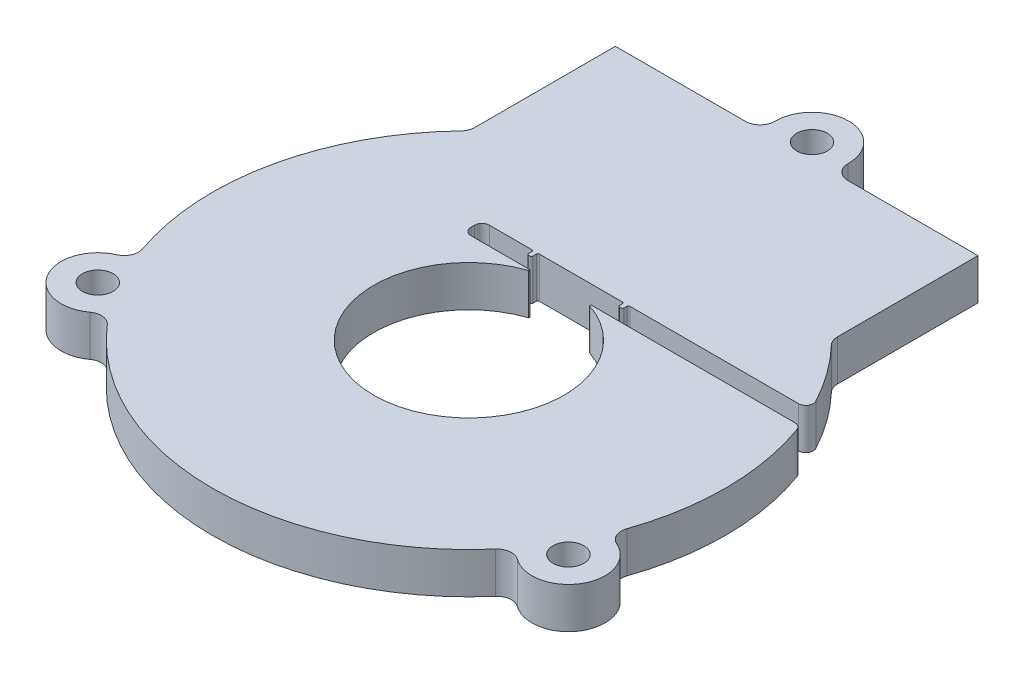
SolidWorks part; units mm, degrees
ref_plane "Front Plane" through (0, 0, 0) normal (0, 0, 1) x (1, 0, 0)
ref_plane "Top Plane" through (0, 0, 0) normal (0, 1, 0) x (1, 0, 0)
ref_plane "Right Plane" through (0, 0, 0) normal (1, 0, 0) x (0, 0, -1)
sketch "Sketch13" plane through (0, 0, 0) normal (0, 1, 0) x (1, 0, 0)
  circle A0 centre (0, 0) radius 35
extrude "Boss-Extrude3" add sketch "Sketch13" along normal blind 5.588
sketch "Sketch14" plane through (0, 5.588, 0) normal (0, 1, 0) x (1, 0, 0)
  line L0 (-24.7478, 24.7497) -> (24.7477, 24.7498)
  line L1 (-24.7478, 24.7497) -> (-24.7479, 44.7452)
  line L2 (24.7477, 24.7498) -> (24.7476, 44.7454)
  line L3 (-24.7479, 44.7452) -> (24.7476, 44.7454)
  line L4 (0, 0) -> (60.4611, -34.8658) construction
  line L5 (0, 0) -> (-56.6044, -32.6614) construction
  line L7 (-3.939, 44.1714) -> (-8.8985, 44.1714)
  line L8 (-3.939, 44.1714) -> (-3.939, 47.547)
  line L9 (-3.939, 47.547) -> (-8.8985, 47.547)
  line L10 (-8.8985, 44.1714) -> (-8.8985, 47.547)
  arc A0 (0, 35) -> (-24.7478, 24.7497) centre (0, 0) ccw construction
  circle A1 centre (0, 0) radius 35 construction
  arc A2 (0, 35) -> (-30.3109, -17.4999) centre (0, 0) ccw construction
  arc A3 (0, 35) -> (30.3118, -17.4984) centre (0, 0) ccw
  arc A4 (0, 35) -> (24.7477, 24.7498) centre (0, 0) ccw construction
  circle A5 centre (32.1365, -18.5413) radius 2.1017
  circle A6 centre (32.1365, -18.5413) radius 4.9951
  circle A7 centre (-32.1465, -18.5162) radius 2.0981
  circle A8 centre (-32.1465, -18.5162) radius 4.9995
extrude "Boss-Extrude4" add sketch "Sketch14" against normal up to surface (5.588 mm away) contours L0 L1 L3 L2 up to face at (0, 0, 35)
sketch "Sketch15" plane through (0, 5.588, 0) normal (0, 1, 0) x (1, 0, 0)
  line L0 (0, 0) -> (0, 62.3966) construction
  line L1 (-0.0001, 44.7453) -> (0, 46.8414) construction
  line L2 (-24.7479, 44.7452) -> (24.7476, 44.7454) construction
  circle A0 centre (0, 46.8414) radius 2.0961
  circle A1 centre (0, 46.8414) radius 4.996
extrude "Boss-Extrude11" add sketch "Sketch15" against normal blind 5.588 contours A1 | A0
extrude "Boss-Extrude12" add sketch "Sketch14<6>" against normal up to surface (5.588 mm away) contours A6 up to face at (0, 0, -29.3038)
sketch "Sketch14<6>" plane through (0, 5.588, 0) normal (0, 1, 0) x (1, 0, 0) same geometry as "Sketch14"
extrude "Boss-Extrude14" add sketch "Sketch14<8>" against normal through all contours L0 A5 region at (32.1365, 5.588, 18.5413)
sketch "Sketch14<8>" plane through (0, 5.588, 0) normal (0, 1, 0) x (1, 0, 0) same geometry as "Sketch14"
hole_wizard "Ø4.2 (4.2) Diameter Hole1" positions "Sketch22" profile "Sketch23" hole size "Ø4.2" standard "ANSI Metric" end condition through all
sketch "Sketch22" plane through (0, 5.588, 0) normal (0, 1, 0) x (1, 0, 0)
  point P0 (32.1248, -18.5356)
sketch "Sketch23" plane through (32.1248, 5.588, 18.5356) normal (1, 0, 0) x (0, 0, 1)
  line L0 (0, 0) -> (0, 5.588)
  line L1 (0, 5.588) -> (2.1, 5.588)
  line L2 (2.1, 5.588) -> (2.1, 0)
  line L5 (2.1, 0) -> (0, 0)
  line L11 (0, -6.35) -> (0, 107.95) construction
  dimension "Thru Hole Dia." = 4.2
  dimension "Thru Hole Depth" = 5.588
extrude "Boss-Extrude15" add sketch "Sketch14<11>" against normal up to surface (5.588 mm away) contours A8 up to face at (32.1248, 0, 20.6356)
sketch "Sketch14<11>" plane through (0, 5.588, 0) normal (0, 1, 0) x (1, 0, 0) same geometry as "Sketch14"
hole_wizard "Ø4.2 (4.2) Diameter Hole2" positions "Sketch26" profile "Sketch27" hole size "Ø4.2" standard "ANSI Metric" end condition through all
sketch "Sketch26" plane through (0, 5.588, 0) normal (0, 1, 0) x (1, 0, 0)
  point P0 (-32.148, -18.5088)
  point P2 (-32.148, -18.5088)
sketch "Sketch27" plane through (-32.148, 5.588, 18.5088) normal (1, 0, 0) x (0, 0, 1)
  line L0 (0, 0) -> (0, 5.588)
  line L1 (0, 5.588) -> (2.1, 5.588)
  line L2 (2.1, 5.588) -> (2.1, 0)
  line L5 (2.1, 0) -> (0, 0)
  line L11 (0, -6.35) -> (0, 107.95) construction
  dimension "Thru Hole Dia." = 4.2
  dimension "Thru Hole Depth" = 5.588
fillet "Fillet4" radius 2 1 edges at (-24.7478, 2.794, -24.7497)
fillet "Fillet6" radius 2 1 edges at (-32.2839, 2.794, 13.5185)
fillet "Fillet7" radius 2 1 edges at (-27.8924, 2.794, 21.1427)
fillet "Fillet8" radius 2 1 edges at (27.8812, 2.794, 21.1574)
fillet "Fillet9" radius 2 1 edges at (32.2715, 2.794, 13.548)
fillet "Fillet10" radius 2 1 edges at (24.7477, 2.794, -24.7498)
fillet "Fillet11" radius 2 1 edges at (4.535, 2.794, -44.7453)
fillet "Fillet12" radius 2 1 edges at (-4.535, 2.794, -44.7453)
sketch "Sketch28" plane through (0, 5.588, 0) normal (0, 1, 0) x (1, 0, 0)
  circle A0 centre (0, 0) radius 5
extrude "Cut-Extrude1" cut sketch "Sketch28" against normal up to surface (5.588 mm away) up to face at (-32.148, 0, 20.6088)
sketch "Sketch29" plane through (0, 5.588, 0) normal (0, 1, 0) x (1, 0, 0)
  circle A0 centre (0, 0) radius 13
extrude "Cut-Extrude2" cut sketch "Sketch29" against normal up to surface (5.588 mm away) contours A0 up to face at (0, 0, 5)
sketch "Sketch30" plane through (0, 5.588, 0) normal (0, 1, 0) x (1, 0, 0)
  line L1 (36.7839, 12.5006) -> (-13.2161, 12.5006)
  line L2 (36.7839, 12.5006) -> (36.7839, 15.0006)
  line L3 (36.7839, 15.0006) -> (-13.2161, 15.0006)
  line L4 (-13.2161, 12.5006) -> (-13.2161, 15.0006)
  dimension "D1" = 50
  dimension "D2" = 2.5
extrude "Cut-Extrude5" cut sketch "Sketch30" against normal up to surface (5.588 mm away) contours L2 L1 L4 L3 up to face at (0, 0, 13)
fillet "Fillet17" radius 0.1 2 edges at (3.5688, 2.794, -12.5006) (-3.5688, 2.794, -12.5006)
fillet "Fillet18" radius 1 1 edges at (31.6225, 2.794, -15.0006)
fillet "Fillet19" radius 1 1 edges at (32.6915, 2.794, -12.5006)
fillet "Fillet20" radius 1 1 edges at (-13.2161, 2.794, -15.0006)
fillet "Fillet21" radius 1 1 edges at (-13.2161, 2.794, -12.5006)
sketch "Sketch34" plane through (0, 5.588, 0) normal (0, 1, 0) x (1, 0, 0)
  line L0 (29.9997, 15.0006) -> (-12.2161, 15.0006) construction
  line L1 (-5.5773, 15.4884) -> (6.1227, 15.4884) construction
  line L2 (-5.5773, 15.4884) -> (-5.5773, 17.0717) construction
  line L3 (-5.5773, 17.0717) -> (6.1227, 17.0717) construction
  line L4 (6.1227, 15.4884) -> (6.1227, 17.0717) construction
  line L5 (-5.5773, 15.0006) -> (-6.1851, 15.0006)
  line L6 (-5.5773, 15.0006) -> (-5.5773, 14.127)
  line L7 (-5.5773, 14.127) -> (-6.1851, 14.127)
  line L8 (-6.1851, 15.0006) -> (-6.1851, 14.127)
  dimension "D1" = 11.7
extrude "Boss-Extrude16" add sketch "Sketch34" against normal up to surface (5.588 mm away) contours L6 L5 L8 L7 up to face at (0, 0, -44.7453)
fillet "Fillet23" radius 0.2 1 edges at (-5.5773, 2.794, -15.0006)
fillet "Fillet24" radius 0.2 1 edges at (-6.1851, 2.794, -15.0006)
fillet "Fillet25" radius 0.2 2 edges at (-5.5773, 2.794, -14.127) (-6.1851, 2.794, -14.127)
sketch "Sketch35" plane through (0, 5.588, 0) normal (0, 1, 0) x (1, 0, 0)
  line L0 (29.9997, 15.0006) -> (-5.3773, 15.0006) construction
  line L1 (-5.5357, 15.1131) -> (6.1676, 15.1131) construction
  line L2 (-5.5357, 15.1131) -> (-5.5357, 16.4786) construction
  line L3 (-5.5357, 16.4786) -> (6.1676, 16.4786) construction
  line L4 (6.1676, 15.1131) -> (6.1676, 16.4786) construction
  line L5 (6.1676, 15.0006) -> (6.7676, 15.0006)
  line L6 (6.1676, 15.0006) -> (6.1676, 14.2006)
  line L7 (6.1676, 14.2006) -> (6.7676, 14.2006)
  line L8 (6.7676, 15.0006) -> (6.7676, 14.2006)
  dimension "D1" = 0.8
  dimension "D2" = 0.6
extrude "Boss-Extrude17" add sketch "Sketch35" against normal up to surface (5.588 mm away) up to face at (0, 0, -44.7453)
fillet "Fillet26" radius 0.2 2 edges at (6.7676, 2.794, -14.2006) (6.1676, 2.794, -14.2006)
fillet "Fillet27" radius 0.2 2 edges at (6.1676, 2.794, -15.0006) (6.7676, 2.794, -15.0006)
